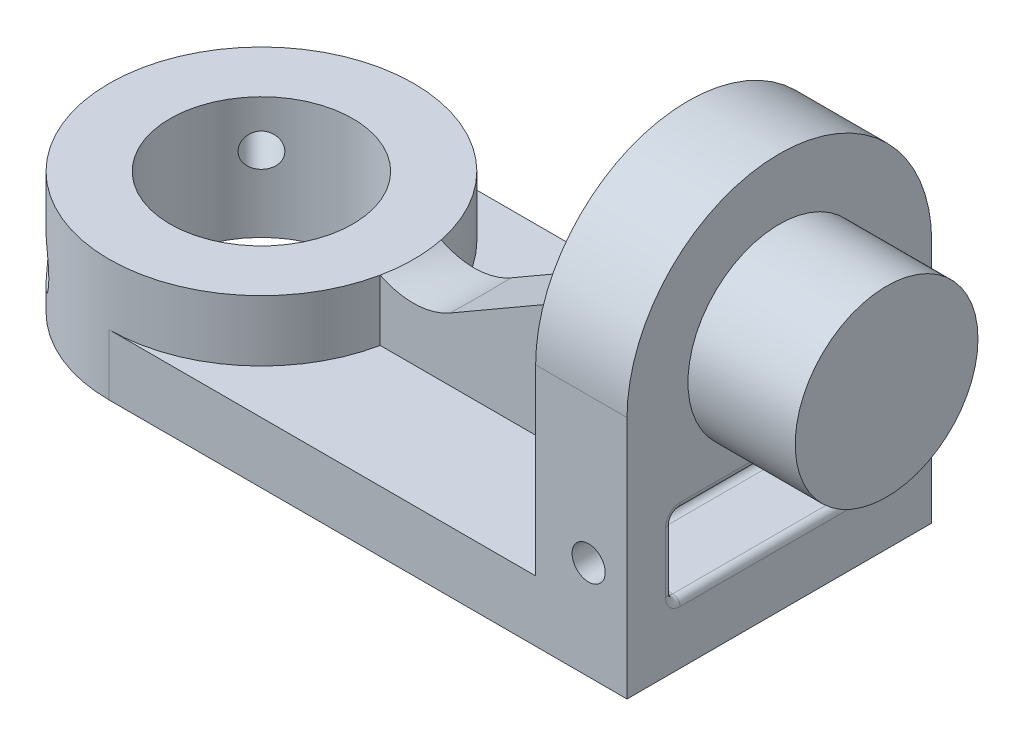
SolidWorks part; units mm, degrees
material "Alloy Steel"
ref_plane "Front Plane" through (0, 0, 0) normal (0, 0, 1) x (1, 0, 0)
ref_plane "Top Plane" through (0, 0, 0) normal (0, 1, 0) x (1, 0, 0)
ref_plane "Right Plane" through (0, 0, 0) normal (1, 0, 0) x (0, 0, -1)
sketch "Sketch1" plane through (0, 0, 0) normal (0, 1, 0) x (1, 0, 0)
  circle A0 centre (0, 0) radius 15.875
  circle A1 centre (0, 0) radius 9.525
  dimension "D1" = 31.75
  dimension "D2" = 19.05
extrude "Boss-Extrude1" add sketch "Sketch1" along normal blind 12.7
sketch "Sketch2" plane through (0, 0, 0) normal (0, 1, 0) x (1, 0, 0)
  line L0 (0, -15.875) -> (53.975, -15.875)
  line L1 (53.975, -15.875) -> (53.975, 15.875)
  line L2 (53.975, 15.875) -> (0, 15.875)
  circle A0 centre (0, 0) radius 15.875 construction
  arc A1 (0, 15.875) -> (0, -15.875) centre (0, 0) cw
  dimension "D1" = 53.975
extrude "Boss-Extrude2" add sketch "Sketch2" along normal blind 6.35 contours L0 L1 L2 A1
sketch "Sketch3" plane through (53.975, 0, 0) normal (1, 0, 0) x (0, 0, -1)
  line L0 (-15.875, 25.4) -> (-15.875, 0)
  line L1 (-15.875, 0) -> (15.875, 0)
  line L2 (15.875, 0) -> (15.875, 25.4)
  line L3 (-15.875, 0) -> (15.875, 0) construction
  line L4 (9.525, 12.7) -> (-9.525, 12.7) construction
  arc A0 (-15.875, 25.4) -> (15.875, 25.4) centre (0, 25.4) cw
  dimension "D1" = 12.7
extrude "Boss-Extrude3" add sketch "Sketch3" against normal blind 9.525 separate body
sketch "Sketch4" plane through (53.975, 0, 0) normal (1, 0, 0) x (0, 0, -1)
  circle A0 centre (0, 25.4) radius 9.525
  dimension "D1" = 19.05
extrude "Boss-Extrude4" add sketch "Sketch4" along normal blind 11.176
sketch "Sketch7" plane through (0, 0, 0) normal (0, 0, 1) x (1, 0, 0)
  line L0 (44.45, 25.4) -> (44.45, 6.35)
  line L1 (0, 6.35) -> (53.975, 6.35) construction
  line L2 (44.45, 25.4) -> (44.45, 0) construction
  line L3 (44.45, 6.35) -> (11.4544, 6.35)
  line L4 (11.4544, 6.35) -> (44.45, 25.4)
  dimension "D1" = 30
extrude "Boss-Extrude5" add sketch "Sketch7" along normal mid plane 6.35
sketch "Sketch8" plane through (53.975, 0, 0) normal (1, 0, 0) x (0, 0, -1)
  line L0 (-15.875, 25.4) -> (-15.875, 0) construction
  line L1 (-11.0998, 14.224) -> (11.1252, 14.224)
  line L2 (-11.0998, 14.224) -> (-11.0998, 6.35)
  line L3 (-11.0998, 6.35) -> (11.1252, 6.35)
  line L4 (11.1252, 14.224) -> (11.1252, 6.35)
  line L5 (-15.875, 0) -> (15.875, 0) construction
  dimension "D1" = 22.225
  dimension "D2" = 4.7752
  dimension "D3" = 7.874
  dimension "D4" = 6.35
extrude "Cut-Extrude1" cut sketch "Sketch8" against normal blind 8.001
sketch "Sketch9" plane through (0, 0, 15.875) normal (0, 0, 1) x (1, 0, 0)
  line L0 (45.974, 14.224) -> (45.974, 6.35) construction
  line L2 (45.974, 6.35) -> (53.975, 6.35) construction
  circle A0 centre (49.9745, 10.287) radius 1.7272
  point P4 (45.974, 10.287)
  point P7 (49.9745, 6.35)
  dimension "D1" = 3.4544
extrude "Cut-Extrude2" cut sketch "Sketch9" against normal through all both and the other way through all
ref_plane "Plane1" through (0, 0, 0) normal (-0.7071, 0, 0.7071) x (0, -1, 0)
ref_plane "Plane2" [suppressed] through (0, 0, 0) normal (-0.7071, 0, -0.7071) x (0, -1, 0)
sketch "Sketch11" plane through (0, 0, 0) normal (-0.7071, 0, -0.7071) x (0, -1, 0)
  line L0 (-12.7, 0) -> (-6.35, 0) construction
  line L1 (-12.7, 0) -> (0, 0) construction
  line L3 (-12.7, 15.875) -> (-12.7, -15.875) construction
  circle A1 centre (-7.874, 0) radius 1.7272
  dimension "D2" = 3.4544
  dimension "D1" = 4.826
extrude "Cut-Extrude3" cut sketch "Sketch11" against normal blind 4.826 and the other way through all
sketch "Sketch15" plane through (0, 0, 0) normal (-0.7071, 0, 0.7071) x (0, -1, 0)
  line L0 (-12.7, 0) -> (0, 0) construction
  line L1 (-12.7, 0) -> (-6.35, 0) construction
  line L2 (0, -15.875) -> (0, 11.2253) construction
  circle A0 centre (-4.826, 0) radius 2.54
  dimension "D1" = 5.08
  dimension "D2" = 4.826
extrude "Cut-Extrude5" cut sketch "Sketch15" along normal through all
fillet "Fillet1" radius 7.62 1 edges at (15.875, 8.9022, 0)
fillet "Fillet2" radius 0.762 2 edges at (44.45, 15.875, 3.175) (44.45, 15.875, -3.175)
fillet "Fillet3" radius 0.762 11 edges at (53.975, 10.287, -11.1252) (53.975, 10.287, 11.0998) (49.9745, 6.35, 11.0998) (45.974, 6.35, -0.0127) (49.9745, 6.35, -11.1252) (53.975, 6.35, -0.0127) (49.9745, 14.224, -11.1252) (45.974, 14.224, -0.0127) (49.9745, 14.224, 11.0998) (53.975, 14.224, -0.0127) (45.974, 10.287, -11.1252)
equation "\"c\"=0.136"
equation "\"D1@Sketch9\"=\"c\""
equation "\"D2@Sketch11\"=\"c\""
